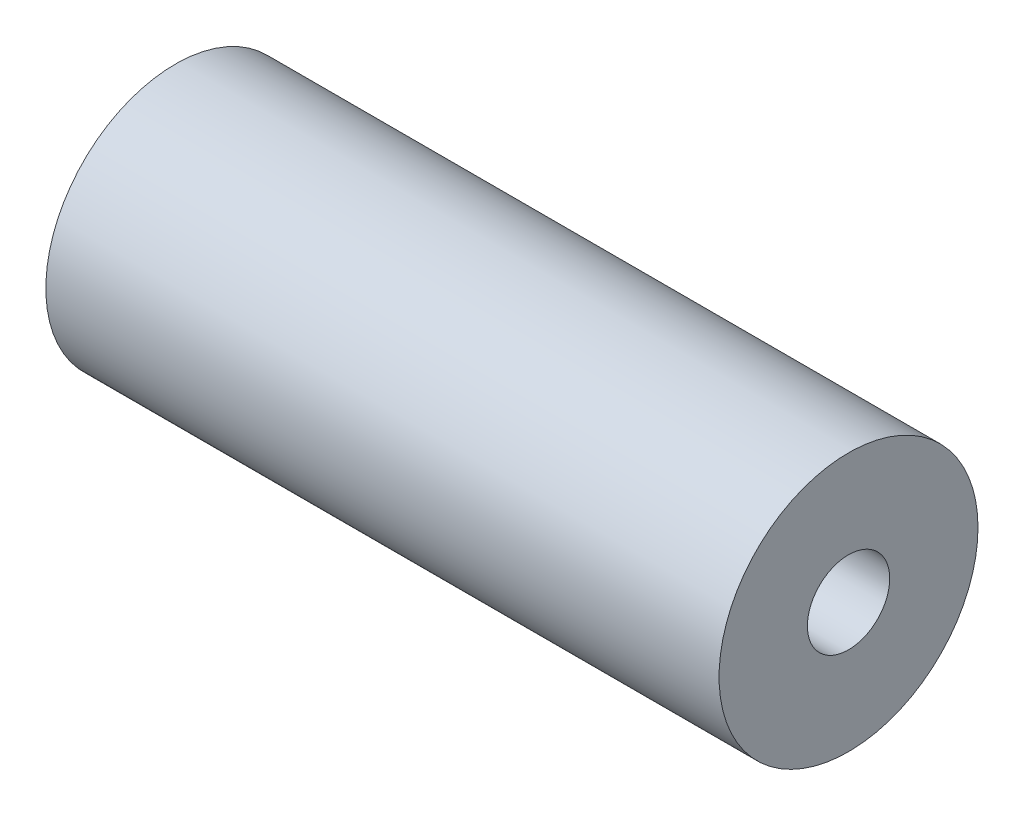
SolidWorks part; units mm, degrees
material "6061-T6 (SS)"
ref_plane "Front Plane" through (0, 0, 0) normal (0, 0, 1) x (1, 0, 0)
ref_plane "Top Plane" through (0, 0, 0) normal (0, 1, 0) x (1, 0, 0)
ref_plane "Right Plane" through (0, 0, 0) normal (1, 0, 0) x (0, 0, -1)
sketch "Sketch1" plane through (0, 0, 0) normal (1, 0, 0) x (0, 0, -1)
  circle A0 centre (0, 0) radius 6.35
  dimension "D1" = 12.7
extrude "Boss-Extrude1" add sketch "Sketch1" along normal mid plane 33.02
hole_wizard "Tap Drill for #10-32 Tap1" positions "Sketch2" profile "Sketch3" hole size "#10-32" standard "ANSI Inch"
sketch "Sketch2" plane through (16.51, 0, 0) normal (1, 0, 0) x (0, 0, -1)
  point P0 (0, 0)
sketch "Sketch3" plane through (16.51, 0, 0) normal (0, 1, 0) x (0, 0, -1)
  line L0 (0, 0) -> (0, 12.1353)
  line L1 (0, 12.1353) -> (2.0193, 10.922)
  line L2 (2.0193, 10.922) -> (2.0193, 0)
  line L5 (2.0193, 0) -> (0, 0)
  line L10 (0, 12.1353) -> (-2.0193, 10.922) construction
  line L11 (0, -6.35) -> (0, 107.95) construction
  dimension "Hole Dia." = 4.0386
  dimension "Hole Depth" = 10.922
  dimension "Drill Angle" = 118
mirror "Mirror1" about plane through (0, 0, 0) normal (1, 0, 0) of "Tap Drill for #10-32 Tap1"
